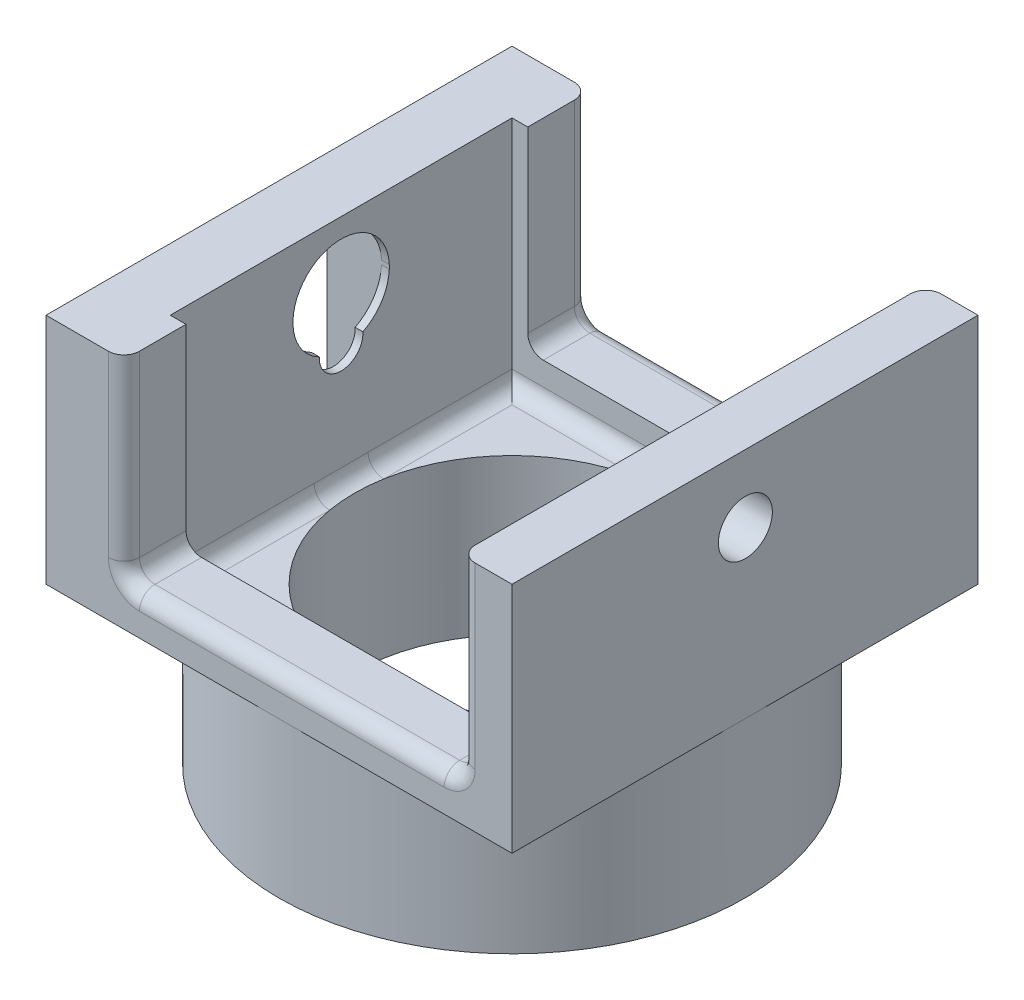
SolidWorks part; units mm, degrees
ref_plane "Front Plane" through (0, 0, 0) normal (0, 0, 1) x (1, 0, 0)
ref_plane "Top Plane" through (0, 0, 0) normal (0, 1, 0) x (1, 0, 0)
ref_plane "Right Plane" through (0, 0, 0) normal (1, 0, 0) x (0, 0, -1)
sketch "Sketch1" plane through (0, 0, 0) normal (0, 1, 0) x (1, 0, 0)
  circle A1 centre (0, 0) radius 20.3
  circle A2 centre (0, 0) radius 30
  dimension "D1" = 40.6
  dimension "D2" = 60
extrude "Boss-Extrude1" add sketch "Sketch1" along normal blind 20
sketch "Sketch3" plane through (0, 20, 0) normal (0, 1, 0) x (1, 0, 0)
  line L7 (-30, -30) -> (30, -30)
  line L8 (-30, -30) -> (-30, 30)
  line L9 (-30, 30) -> (30, 30)
  line L10 (30, -30) -> (30, 30)
  circle A3 centre (0, 0) radius 30 construction
extrude "Extrude-Thin1" add sketch "Sketch3" along normal blind 30 thin contours L8 L9 L10 L7 thin type one direction reverse wall 8
fillet "Fillet1" radius 2 4 edges at (0, 20, 22) (22, 20, 0) (0, 20, -22) (-22, 20, 0)
sketch "Sketch5" plane through (-30, 0, 0) normal (-1, 0, 0) x (0, 0, 1)
  line L1 (-6.2, 24.993) -> (6.2, 24.993)
  line L2 (-6.2, 24.993) -> (-6.2, 47.493)
  line L3 (-6.2, 47.493) -> (6.2, 47.493)
  line L4 (6.2, 24.993) -> (6.2, 47.493)
  line L5 (-6.2, 24.993) -> (6.2, 47.493) construction
  line L6 (-6.2, 47.493) -> (6.2, 24.993) construction
  point P0 (0, 36.243)
  dimension "D1" = 22.5
  dimension "D2" = 12.4
extrude "Cut-Extrude1" cut sketch "Sketch5" against normal blind 7
sketch "Sketch6" plane through (-23, 0, 0) normal (-1, 0, 0) x (0, 0, 1)
  line L1 (-6.2, 47.493) -> (6.2, 47.493)
  line L2 (-6.2, 47.493) -> (-6.2, 24.993)
  line L3 (-6.2, 24.993) -> (6.2, 24.993)
  line L4 (6.2, 47.493) -> (6.2, 24.993)
  circle A0 centre (0, 41.288) radius 2.45
  circle A1 centre (0, 41.288) radius 6.205
  circle A2 centre (0, 35.588) radius 2.81
  dimension "D1" = 4.9
  dimension "D3" = 5.62
  dimension "D2" = 6.205
  dimension "D4" = 5.7
extrude "Cut-Extrude2" cut sketch "Sketch6" against normal blind 7 contours A2 A1 L4 L2 A0 | A0 | A1 A2 | A1 A2 region at (-23, 45.6397, 4.1803) region at (-23, 36.6195, 0) region at (-23, 34.2495, 0) region at (-23, 41.288, 0)
sketch "Sketch10" plane through (0, 50, 0) normal (0, 1, 0) x (1, 0, 0)
  line L1 (23.2618, 32.8453) -> (-19.9717, 32.8453)
  line L2 (23.2618, 32.8453) -> (23.2618, -33.2315)
  line L3 (23.2618, -33.2315) -> (-19.9717, -33.2315)
  line L4 (-19.9717, 32.8453) -> (-19.9717, -33.2315)
extrude "Cut-Extrude3" cut sketch "Sketch10" against normal blind 25 contours L1 L4 L3 L2
fillet "Fillet2" radius 2 9 edges at (-19.9717, 37.5, 30) (23.2618, 37.5, -30) (-19.9717, 37.5, -30) (1.6451, 25, 30) (1.6451, 25, -30) (23.2618, 37.5, 30) (23.2618, 25, 0) (-19.9717, 25, -26) (-19.9717, 25, 26)
sketch "Sketch11" plane through (23.2618, 0, 0) normal (-1, 0, 0) x (0, 0, 1)
  circle A0 centre (-0.0483, 41.3142) radius 6.2599
  circle A1 centre (-0.0483, 41.3142) radius 3.475
  dimension "7" = 6.95
extrude "Cut-Extrude5" cut sketch "Sketch11" along normal blind 4 and the other way blind 17 contours A1 region at (23.2618, 41.3142, -0.0483)
